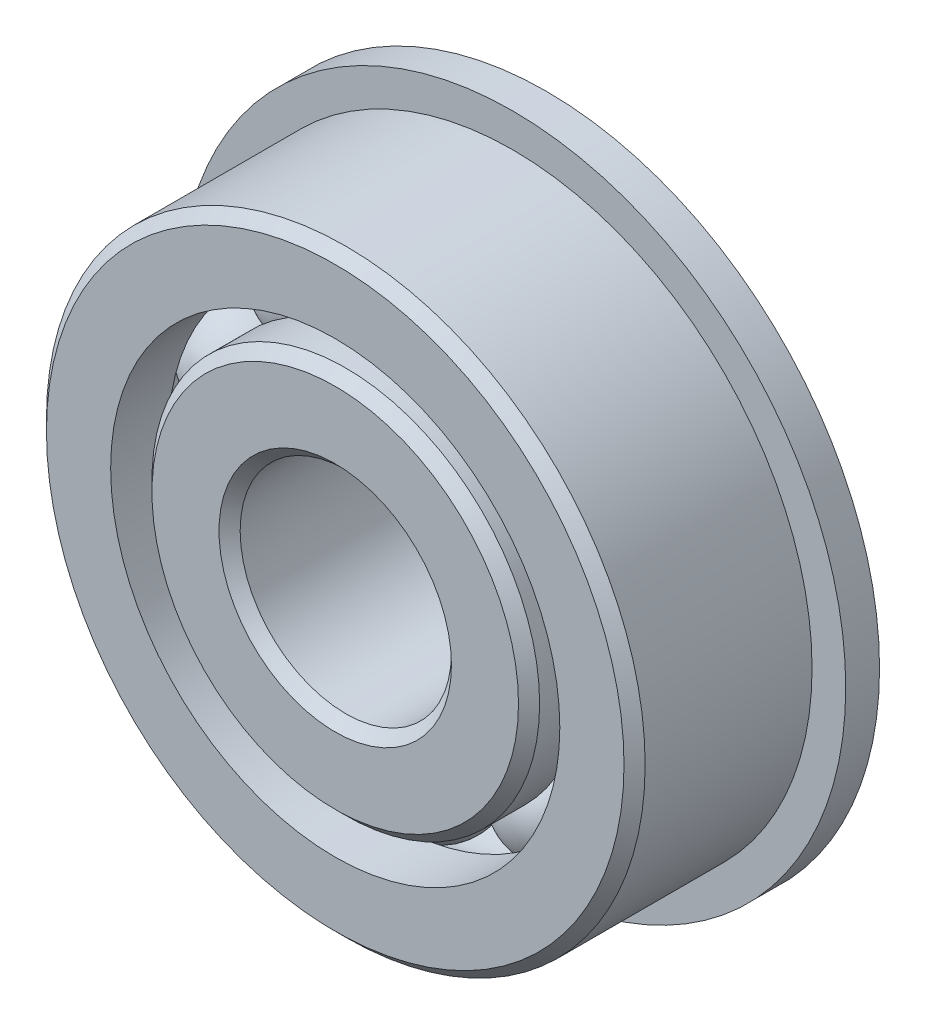
SolidWorks part; units mm, degrees
ref_plane "Front Plane" through (0, 0, 0) normal (0, 0, 1) x (1, 0, 0)
ref_plane "Top Plane" through (0, 0, 0) normal (0, 1, 0) x (1, 0, 0)
ref_plane "Right Plane" through (0, 0, 0) normal (1, 0, 0) x (0, 0, -1)
sketch "Sketch1" plane through (0, 0, 0) normal (1, 0, 0) x (0, 0, -1)
  line L0 (-4.7625, 0) -> (4.7625, 0) construction
  line L1 (0, 13.4937) -> (0, -13.4937) construction
  line L2 (4.2863, 13.4938) -> (-4.2862, 13.4937)
  line L3 (-4.2862, 13.4937) -> (-4.7625, 13.0175)
  line L4 (-4.7625, 13.0175) -> (-4.7625, 10.1235)
  line L5 (-4.7625, 10.1235) -> (-2.1632, 10.1235)
  line L6 (4.7625, 10.1235) -> (2.1632, 10.1235)
  line L7 (4.7625, 13.0175) -> (4.7625, 10.1235)
  line L8 (4.2863, 13.4938) -> (4.7625, 13.0175)
  line L9 (0, 13.4937) -> (0, 9.1281) construction
  line L10 (0, 9.1281) -> (0, 4.7625) construction
  line L11 (4.7625, 8.7376) -> (4.7625, -8.7376) construction
  line L12 (-4.7625, 4.7625) -> (4.7625, 4.7625) construction
  line L13 (0, 6.7469) -> (0, 4.7625) construction
  line L14 (0, 11.5094) -> (0, 13.4937) construction
  line L15 (4.7625, 8.7376) -> (0, 8.7376) construction
  circle A1 centre (0, 9.1281) radius 2.3813 construction
  arc A2 (-2.1632, 10.1235) -> (2.1632, 10.1235) centre (0, 9.1281) cw
  point P14 (0, 4.7625)
  point P22 (0, 6.7469)
  point P23 (0, 11.5094)
  dimension "D3" = 4.7625
  dimension "Width" = 9.525
  dimension "OD" = 26.9875
  dimension "D1" = 45
  dimension "D2" = 0.4763
  dimension "D4" = 17.4752
  dimension "D5" = 2.7718
  dimension "D6" = 1.3859
revolve "Revolve1" add sketch "Sketch1" angle 360 about L0
sketch "Sketch3" plane through (0, 0, 0) normal (1, 0, 0) x (0, 0, -1)
  line L1 (-4.7625, 13.0175) -> (-4.7625, 10.1235) construction
  line L2 (-4.2862, 13.4937) -> (-4.7625, 13.0175) construction
  line L3 (-4.7625, 8.1328) -> (-4.7625, 5.2387) construction
  line L4 (-4.7625, 5.2387) -> (-4.7625, 8.2614)
  line L5 (-4.7625, 5.2387) -> (-4.2863, 4.7625)
  line L6 (-4.2863, 4.7625) -> (5.8864, 4.7625)
  line L7 (-4.7625, 13.0175) -> (-4.7625, -13.0175) construction
  line L8 (5.8864, 4.7625) -> (6.3627, 5.2387)
  line L9 (0, 0) -> (6.3627, 0) construction
  line L13 (4.2863, 13.4938) -> (4.7625, 13.0175) construction
  line L14 (-4.7625, 8.2614) -> (-4.2863, 8.7376)
  line L15 (-4.2863, 8.7376) -> (-2.349, 8.7376)
  line L16 (2.349, 8.7376) -> (5.8864, 8.7376)
  line L17 (5.8864, 8.7376) -> (6.3627, 8.2614)
  line L18 (6.3627, 8.2614) -> (6.3627, 5.2387)
  circle A0 centre (0, 9.1281) radius 2.3812 construction
  arc A1 (-2.349, 8.7376) -> (2.349, 8.7376) centre (0, 9.1281) ccw
  dimension "D1" = 45
  dimension "Ring Wd" = 11.1252
  dimension "Inner Ring OD" = 17.4752
revolve "Revolve3" add sketch "Sketch3" angle 360 about L0
sketch "Sketch6" plane through (0, 0, 0) normal (1, 0, 0) x (0, 0, -1)
  line L1 (4.7625, 10.1235) -> (3.2385, 10.1235)
  line L2 (4.7625, 10.1235) -> (4.7625, 15.0114)
  line L3 (4.7625, 15.0114) -> (3.2385, 15.0114)
  line L4 (3.2385, 10.1235) -> (3.2385, 15.0114)
  line L5 (4.7625, 0) -> (-4.7625, 0) construction
  dimension "Flange OD" = 30.0228
  dimension "Flange Thickness" = 1.524
revolve "Revolve6" add sketch "Sketch6" angle 360 about L5
sketch "Sketch4" plane through (0, 0, 0) normal (1, 0, 0) x (0, 0, -1)
  line L0 (-2.3813, 9.1281) -> (2.3813, 9.1281)
  circle A0 centre (0, 9.1281) radius 2.3812 construction
  arc A1 (2.3813, 9.1281) -> (-2.3813, 9.1281) centre (0, 9.1281) ccw
revolve "Revolve4" add sketch "Sketch4" angle 360 about L0
ref_axis "Axis1" through (0, 0, -4.7625) along (0, 0, 1)
pattern_circular "CirPattern1" count 10 every 36 about axis through (0, 0, -4.7625) along (0, 0, 1) of bodies 104
sketch "Sketch5" plane through (0, 0, 0) normal (1, 0, 0) x (0, 0, -1)
  line L0 (-4.7625, 10.1235) -> (-2.1632, 10.1235) construction
  line L1 (-4.5244, 10.1235) -> (-2.349, 10.1235)
  line L2 (-4.5244, 10.1235) -> (-4.5244, 8.7376)
  line L3 (-4.5244, 8.7376) -> (-2.349, 8.7376)
  line L4 (-2.349, 10.1235) -> (-2.349, 8.7376)
  line L6 (4.7625, 10.1235) -> (2.1632, 10.1235) construction
  line L7 (4.5244, 10.1235) -> (2.349, 10.1235)
  line L8 (4.5244, 10.1235) -> (4.5244, 8.7376)
  line L9 (4.5244, 8.7376) -> (2.349, 8.7376)
  line L10 (2.349, 10.1235) -> (2.349, 8.7376)
  line L12 (-4.2862, 13.4937) -> (-4.7625, 13.0175) construction
  line L13 (4.7625, 8.7376) -> (0, 8.7376) construction
  line L15 (-4.2863, 8.7376) -> (-2.349, 8.7376) construction
  line L16 (4.5244, 10.1235) -> (4.5244, 13.2556) construction
  line L17 (4.2863, 13.4938) -> (4.7625, 13.0175) construction
  point P18 (-4.5244, 13.2556)
revolve "Revolve5" [suppressed] add sketch "Sketch5" angle 360 about L0
equation "\"D2@Sketch1\" = \"Width@Sketch1\"*.05"
equation "\"D2@CirPattern1\" = 360/\"Balls@CirPattern1\""
equation "\"D4@Sketch1\"=\"Inner Ring OD@Sketch3\""
equation "\"D3@Sketch1\"=\"Width@Sketch1\"/2."
equation "\"D6@Sketch1\"=\"D5@Sketch1\"/2"
